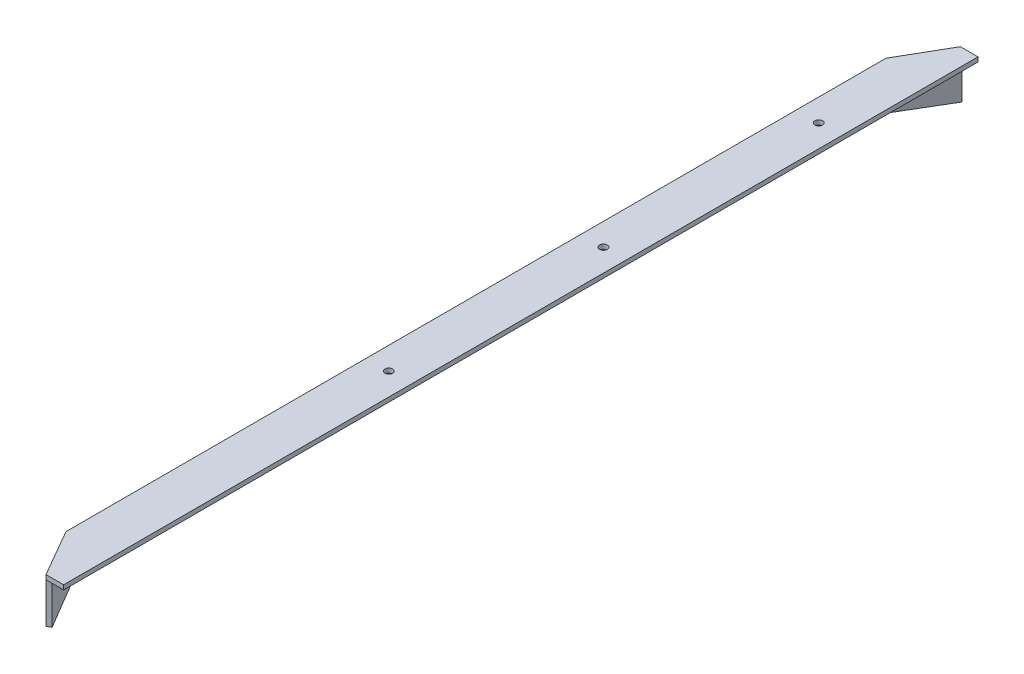
SolidWorks part; units mm, degrees
material "1.0116 (S235J2G3)"
ref_plane "Front Plane" through (0, 0, 0) normal (0, 0, 1) x (1, 0, 0)
ref_plane "Top Plane" through (0, 0, 0) normal (0, 1, 0) x (1, 0, 0)
ref_plane "Right Plane" through (0, 0, 0) normal (1, 0, 0) x (0, 0, -1)
sketch "Sketch1" plane through (0, 0, 0) normal (0, 0, 1) x (1, 0, 0)
  line L6 (0, 0) -> (0, 70)
  line L7 (0, 70) -> (70, 70)
  line L8 (70, 70) -> (70, 63)
  line L9 (70, 63) -> (7, 63)
  line L10 (7, 63) -> (7, 0)
  line L11 (7, 0) -> (0, 0)
  dimension "D1" = 70
  dimension "D2" = 70
  dimension "D3" = 7
  dimension "D4" = 7
extrude "Boss-Extrude1" add sketch "Sketch1" along normal blind 640
sketch "Sketch21" plane through (0, 0, 0) normal (0, 0, -1) x (-1, 0, 0)
  line L0 (0, 70) -> (-70, 70) construction
  line L1 (-70, 70) -> (-70, 0) construction
  line L2 (-70, 0) -> (0, 0) construction
  line L3 (0, 0) -> (0, 69.2595) construction
sketch "Sketch23" plane through (0, 0, 0) normal (0, 1, 0) x (1, 0, 0)
  line L0 (0, -640) -> (42.5, -713.6122)
  line L1 (42.5, -713.6122) -> (48.5622, -710.1122)
  line L2 (48.5622, -710.1122) -> (7, -640)
  line L3 (7, -640) -> (0, -640)
  line L4 (0, -38.5) -> (0, 38.5) construction
  dimension "D1" = 7
  dimension "D2" = 210
  dimension "D3" = 85
extrude "Boss-Extrude2" add sketch "Sketch23" along normal blind 63
sketch "Sketch25" plane through (0, 63, 0) normal (0, 1, 0) x (1, 0, 0)
  line L0 (70, -640) -> (0, -640)
  line L1 (70, -640) -> (70, 0) construction
  line L2 (7, -640) -> (70, -640) construction
  line L3 (0, -640) -> (42.5, -713.6122) construction
  line L4 (0, -640) -> (42.5, -713.6122)
  line L5 (42.5, -713.6122) -> (48.5622, -710.1122) construction
  line L6 (42.5, -713.6122) -> (70, -713.6122)
  line L7 (70, -713.6122) -> (70, -640)
extrude "Boss-Extrude3" add sketch "Sketch25" along normal blind 7
mirror "Mirror1" about plane through (0, 0, 0) normal (0, 0, 1) of bodies 113 116
sketch "Sketch27" plane through (0, 70, 0) normal (0, 1, 0) x (1, 0, 0)
  line L0 (70, -713.6122) -> (70, 713.6122) construction
  circle A0 centre (35, 500) radius 6
  circle A1 centre (35, 164) radius 6
  circle A2 centre (35, -171) radius 6
  dimension "D1" = 12
  dimension "D2" = 12
  dimension "D3" = 12
  dimension "D4" = 336
  dimension "D5" = 335
  dimension "D6" = 35
  dimension "D7" = 35
  dimension "D8" = 35
  dimension "D9" = 500
extrude "Cut-Extrude6" cut sketch "Sketch27" against normal blind 10 and the other way blind 10
